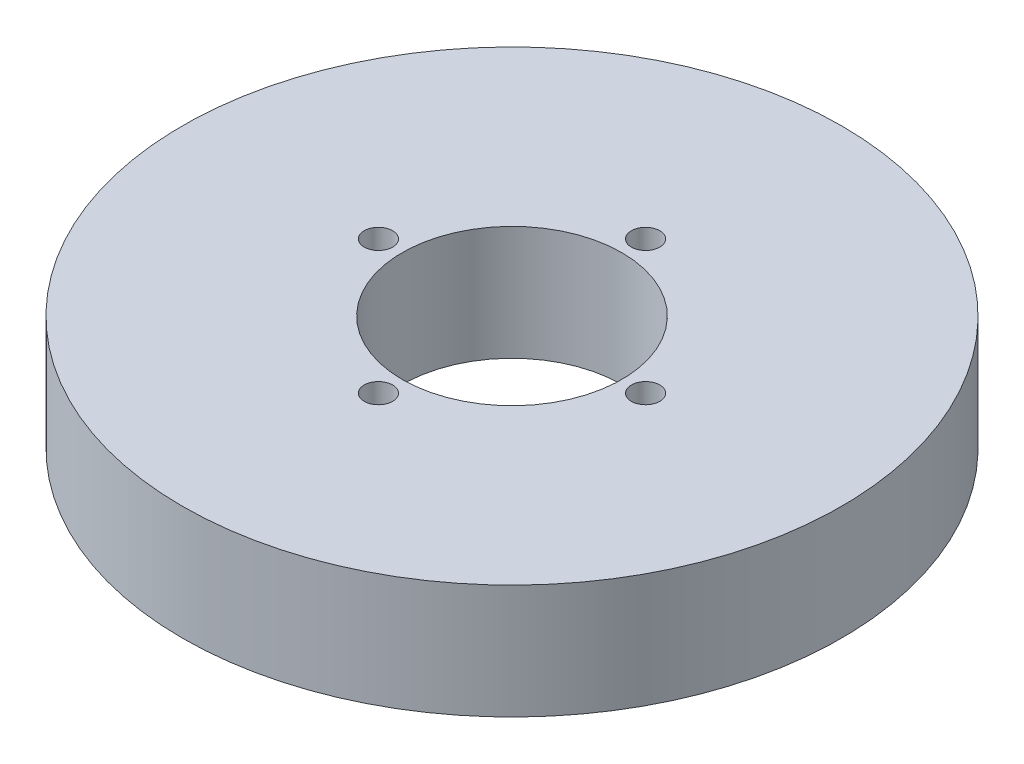
SolidWorks part; units mm, degrees
ref_plane "Front Plane" through (0, 0, 0) normal (0, 0, 1) x (1, 0, 0)
ref_plane "Top Plane" through (0, 0, 0) normal (0, 1, 0) x (1, 0, 0)
ref_plane "Right Plane" through (0, 0, 0) normal (1, 0, 0) x (0, 0, -1)
sketch "Sketch1" plane through (0, 0, 0) normal (0, 1, 0) x (1, 0, 0)
  circle A0 centre (0, 0) radius 37.5
  dimension "FLANGE_OD" = 75
extrude "Boss-Extrude1" add sketch "Sketch1" along normal blind 13
sketch "Sketch2" plane through (0, 0, 0) normal (0, 1, 0) x (1, 0, 0)
  circle A0 centre (0, 0) radius 12.5
  dimension "BORE_D" = 25
extrude "Cut-Extrude1" cut sketch "Sketch2" along normal through all
sketch "Sketch3" plane through (0, 13, 0) normal (0, 1, 0) x (1, 0, 0)
  circle A0 centre (0, 0) radius 15.1994 construction
  circle A1 centre (-15.1994, 0) radius 1.6181
  dimension "BOLT_D" = 3.2362
  dimension "BOLT_PCD" = 30.3987
extrude "Cut-Extrude2" cut sketch "Sketch3" against normal blind 12.5781
pattern_circular "CirPattern1" count 4 over 360 about axis through (0, 0, 0) along (0, 1, 0) of "Cut-Extrude2"
